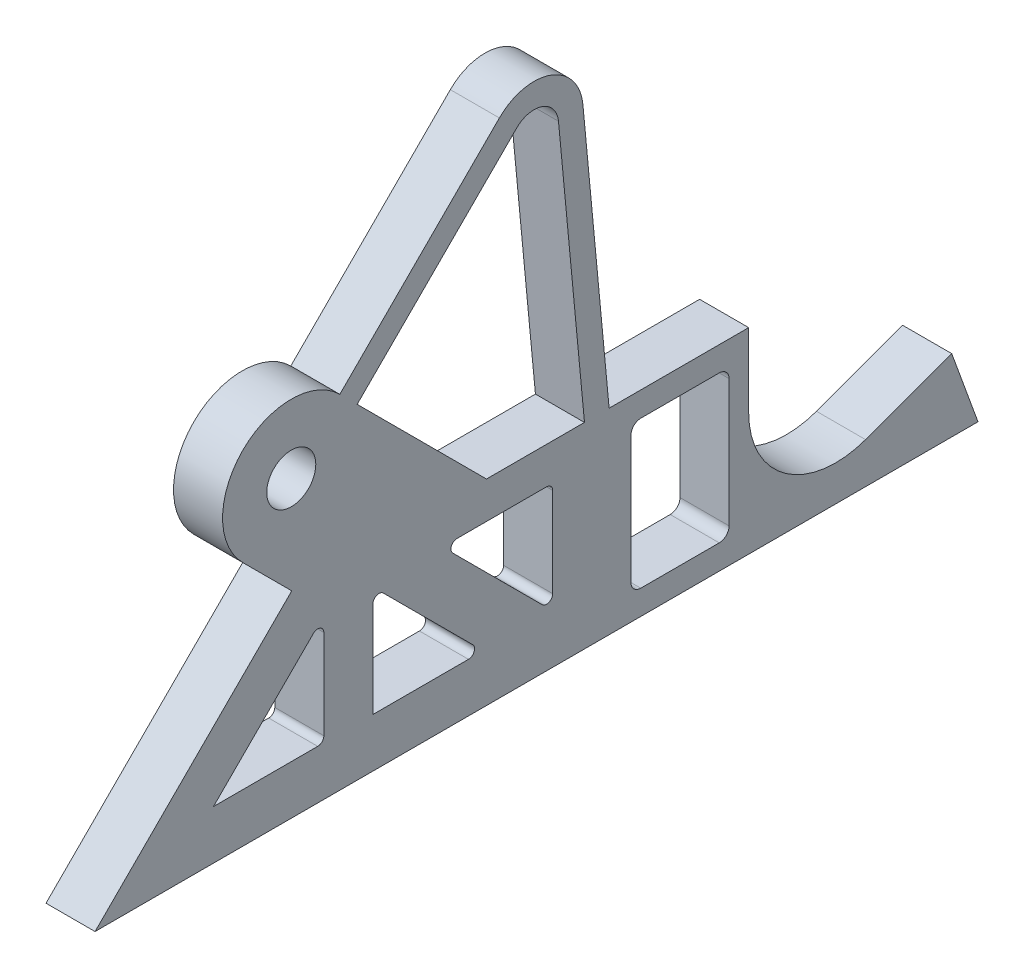
SolidWorks part; units mm, degrees
material "6061 Alloy"
ref_plane "Front Plane" through (0, 0, 0) normal (0, 0, 1) x (1, 0, 0)
ref_plane "Top Plane" through (0, 0, 0) normal (0, 1, 0) x (1, 0, 0)
ref_plane "Right Plane" through (0, 0, 0) normal (1, 0, 0) x (0, 0, -1)
sketch "Sketch1" plane through (0, 0, 0) normal (1, 0, 0) x (0, 0, -1)
  line L0 (114.3, 0) -> (-114.3, 0)
  line L1 (-114.3, 0) -> (-63.3724, 50.9276)
  line L2 (-63.3724, 50.9276) -> (-76.0724, 63.6276)
  line L3 (-50.9276, 88.7724) -> (-12.9553, 50.8)
  line L6 (114.3, 0) -> (95.8103, 50.8)
  line L8 (-12.9553, 50.8) -> (95.8103, 50.8)
  line L13 (85.18, 10.567) -> (107.4974, 18.6899)
  line L14 (54.9275, 31.75) -> (54.9275, 50.8)
  line L15 (-50.9276, 88.7724) -> (-9.6185, 130.0815)
  line L16 (18.7947, 50.8) -> (12.0049, 122.3019)
  line L17 (12.4732, 50.1997) -> (5.6834, 121.7016)
  line L18 (-46.4375, 84.2822) -> (-5.1283, 125.5914)
  arc A0 (-76.0724, 63.6276) -> (-50.9276, 88.7724) centre (-63.5, 76.2) cw
  circle A1 centre (-63.5, 76.2) radius 6.35
  circle A2 centre (77.47, 31.75) radius 22.5425
  arc A4 (12.0049, 122.3019) -> (-9.6185, 130.0815) centre (-0.6382, 121.1013) ccw
  arc A5 (5.6834, 121.7016) -> (-5.1283, 125.5914) centre (-0.6382, 121.1013) ccw
  point P4 (0, 0)
  dimension "D2" = 76.2
  dimension "D3" = 17.78
  dimension "D6" = 12.7
  dimension "D7" = 45.085
  dimension "D11" = 36.83
  dimension "D12" = 76.2
  dimension "D13" = 12.7
  dimension "D1" = 45
  dimension "D4" = 50.8
  dimension "D5" = 228.6
  dimension "D8" = 70
  dimension "D9" = 50.8
  dimension "D10" = 31.75
  dimension "D14" = 31.75
  dimension "D15" = 6.35
extrude "Boss-Extrude1" add sketch "Sketch1" along normal blind 12.7 contours A0 L2 L1 L0 L3 A1 | A5 L17 L8 L16 A4 L15 L3 L18 region at (0, 30.1646, 15.5647) region at (0, 108.6604, 29.5066)
sketch "Sketch2" plane through (12.7, 0, 0) normal (1, 0, 0) x (0, 0, -1)
  line L1 (24.4475, 44.45) -> (49.8475, 44.45)
  line L2 (24.4475, 44.45) -> (24.4475, 6.35)
  line L3 (24.4475, 6.35) -> (49.8475, 6.35)
  line L4 (49.8475, 44.45) -> (49.8475, 6.35)
  line L5 (-12.9553, 50.8) -> (12.4162, 50.8) construction
  line L6 (54.9275, 31.75) -> (54.9275, 50.8) construction
  dimension "D1" = 25.4
  dimension "D2" = 38.1
  dimension "D3" = 6.35
  dimension "D4" = 5.08
extrude "Cut-Extrude1" cut sketch "Sketch2" against normal through all
fillet "Fillet1" radius 2.54 4 edges at (6.35, 6.35, -24.4475) (6.35, 6.35, -49.8475) (6.35, 44.45, -49.8475) (6.35, 44.45, -24.4475)
sketch "Sketch3" plane through (12.7, 0, 0) normal (1, 0, 0) x (0, 0, -1)
  line L0 (-83.6395, 12.7) -> (-55.0645, 41.275)
  line L1 (-55.0645, 41.275) -> (-55.0645, 12.7)
  line L2 (-55.0645, 12.7) -> (-83.6395, 12.7)
  line L3 (-42.3645, 41.275) -> (-42.3645, 12.7)
  line L4 (-42.3645, 12.7) -> (-13.7895, 12.7)
  line L5 (-13.7895, 12.7) -> (-42.3645, 41.275)
  line L6 (-24.404, 41.275) -> (4.171, 41.275)
  line L7 (4.171, 41.275) -> (4.171, 12.7)
  line L8 (4.171, 12.7) -> (-24.404, 41.275)
  line L9 (-114.3, 0) -> (-63.3724, 50.9276) construction
  line L10 (114.3, 0) -> (-114.3, 0) construction
  line L11 (-12.9553, 50.8) -> (12.4162, 50.8) construction
  point P15 (0, 0)
  point P17 (0, 0)
  point P18 (0, 0)
  dimension "D1" = 12.7
  dimension "D2" = 12.7
  dimension "D3" = 9.525
  dimension "D5" = 12.7
  dimension "D6" = 12.7
extrude "Cut-Extrude2" cut sketch "Sketch3" against normal up to next
fillet "Fillet2" radius 1.5875 7 edges at (6.35, 12.7, 55.0645) (6.35, 12.7, 13.7895) (6.35, 12.7, -4.171) (6.35, 41.275, -4.171) (6.35, 41.275, 24.404) (6.35, 41.275, 42.3645) (6.35, 41.275, 55.0645)
